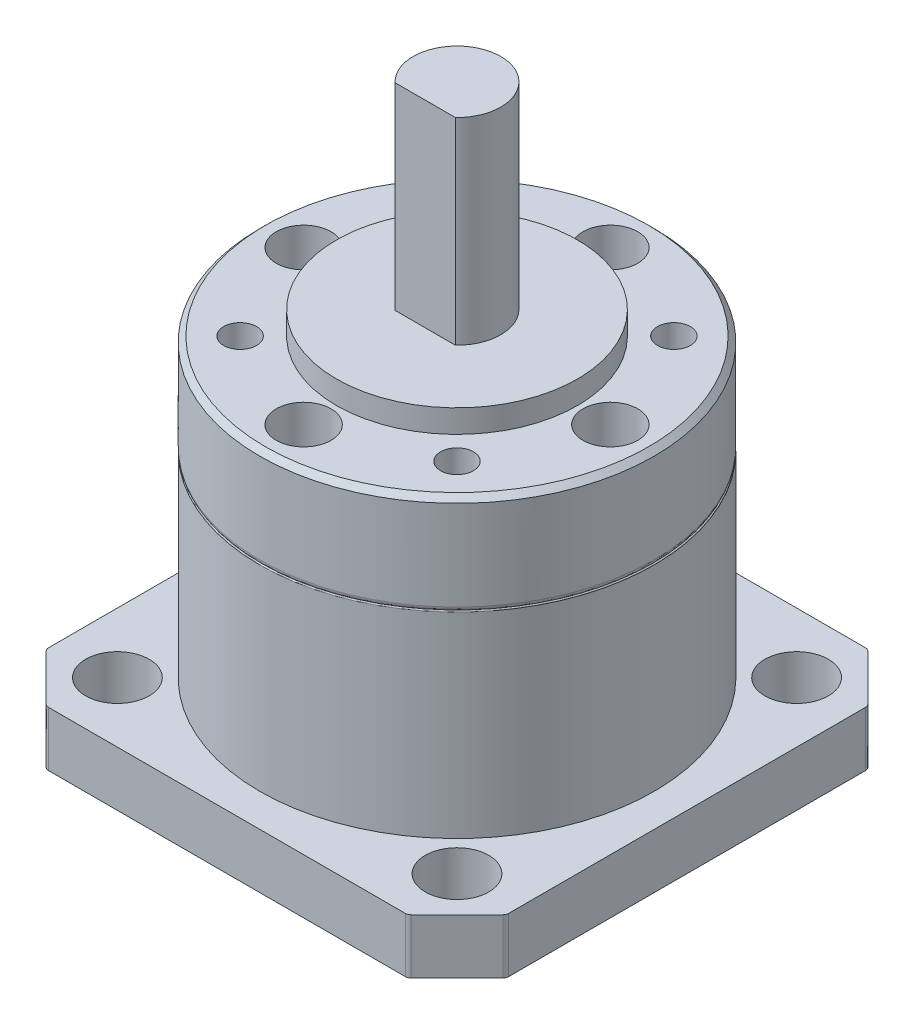
SolidWorks part; units mm, degrees
material "Plain Carbon Steel"
ref_plane "Front Plane" through (0, 0, 0) normal (0, 0, 1) x (1, 0, 0)
ref_plane "Top Plane" through (0, 0, 0) normal (0, 1, 0) x (1, 0, 0)
ref_plane "Right Plane" through (0, 0, 0) normal (1, 0, 0) x (0, 0, -1)
sketch "Sketch1" plane through (0, 0, 0) normal (0, 1, 0) x (1, 0, 0)
  line L0 (4.5, 0) -> (37.5, 0)
  line L1 (42, 4.5) -> (42, 37.5)
  line L2 (37.5, 42) -> (4.5, 42)
  line L3 (0, 37.5) -> (0, 4.5)
  line L4 (4.5, 42) -> (0, 37.5)
  line L5 (42, 37.5) -> (37.5, 42)
  line L6 (37.5, 0) -> (42, 4.5)
  line L7 (0, 4.5) -> (4.5, 0)
  line L8 (5.5, 36.5) -> (0, 36.5) construction
  line L9 (36.5, 36.5) -> (42, 36.5) construction
  line L10 (5.5, 36.5) -> (5.5, 42) construction
  line L11 (5.5, 5.5) -> (5.5, 0) construction
  circle A0 centre (5.5, 36.5) radius 2.9
  circle A1 centre (36.5, 36.5) radius 2.9
  circle A2 centre (36.5, 5.5) radius 2.9
  circle A3 centre (5.5, 5.5) radius 2.9
  point P0 (0, 0)
  point P1 (42, 0)
  point P4 (42, 42)
  point P5 (0, 42)
  dimension "D2" = 5.8
  dimension "D3" = 31
  dimension "D1" = 42
extrude "Boss-Extrude1" add sketch "Sketch1" along normal blind 5
sketch "Sketch2" plane through (0, 5, 0) normal (0, 1, 0) x (1, 0, 0)
  line L0 (21, 42) -> (21, 21) construction
  line L1 (37.5, 42) -> (4.5, 42) construction
  line L2 (21, 21) -> (0, 21) construction
  line L3 (0, 37.5) -> (0, 4.5) construction
  circle A0 centre (21, 21) radius 18
  dimension "D1" = 36
extrude "Boss-Extrude2" add sketch "Sketch2" along normal blind 18
fillet "Fillet1" radius 0.1 1 edges at (21, 23, -3)
fillet "Fillet2" radius 0.5 8 edges at (37.5, 2.5, -42) (4.5, 2.5, -42) (0, 2.5, -37.5) (42, 2.5, -37.5) (37.5, 2.5, 0) (42, 2.5, -4.5) (0, 2.5, -4.5) (4.5, 2.5, 0)
sketch "Sketch4" plane through (0, 23, 0) normal (0, 1, 0) x (1, 0, 0)
  circle A0 centre (21, 21) radius 18
  dimension "D1" = 36
extrude "Boss-Extrude3" add sketch "Sketch4" along normal blind 9
fillet "Fillet3" radius 0.5 1 edges at (21, 23, -3)
chamfer "Chamfer1" distance 0.5 angle 45 1 edges at (21, 32, -3)
sketch "Sketch6" plane through (0, 32, 0) normal (0, 1, 0) x (1, 0, 0)
  line L0 (21, 21) -> (21, 35) construction
  line L1 (21, 21) -> (35, 21) construction
  line L2 (21, 21) -> (21, 7) construction
  line L3 (21, 21) -> (7, 21) construction
  line L4 (21, 21) -> (11.1005, 30.8995) construction
  line L5 (21, 21) -> (30.8995, 30.8995) construction
  line L6 (21, 21) -> (30.8995, 11.1005) construction
  line L7 (21, 21) -> (11.1005, 11.1005) construction
  circle A1 centre (7, 21) radius 2.5
  circle A2 centre (21, 35) radius 2.5
  circle A3 centre (35, 21) radius 2.5
  circle A4 centre (21, 7) radius 2.5
  circle A5 centre (11.1005, 11.1005) radius 1.5
  circle A6 centre (11.1005, 30.8995) radius 1.5
  circle A7 centre (30.8995, 30.8995) radius 1.5
  circle A8 centre (30.8995, 11.1005) radius 1.5
  dimension "D3" = 5
  dimension "D4" = 3
  dimension "D1" = 14
  dimension "D2" = 45
extrude "Cut-Extrude1" cut sketch "Sketch6" against normal blind 9
sketch "Sketch7" plane through (0, 32, 0) normal (0, 1, 0) x (1, 0, 0)
  circle A0 centre (21, 21) radius 11
  dimension "D1" = 22
extrude "Boss-Extrude4" add sketch "Sketch7" along normal blind 2.1
sketch "Sketch8" plane through (0, 34.1, 0) normal (0, 1, 0) x (1, 0, 0)
  line L0 (18.245, 18.1) -> (23.755, 18.1)
  arc A0 (23.755, 18.1) -> (18.245, 18.1) centre (21, 21) ccw
  dimension "D1" = 8
  dimension "D2" = 2.9
extrude "Boss-Extrude5" add sketch "Sketch8" along normal blind 18
